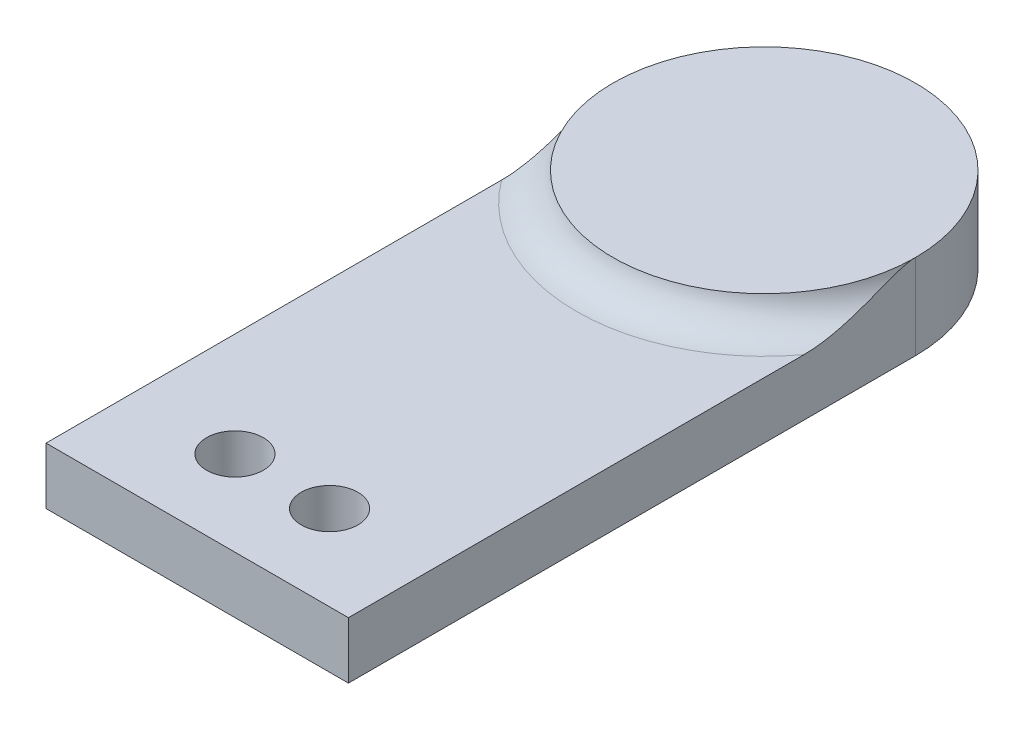
SolidWorks part; units mm, degrees
ref_plane "Plano frontal" through (0, 0, 0) normal (0, 0, 1) x (1, 0, 0)
ref_plane "Plano superior" through (0, 0, 0) normal (0, 1, 0) x (1, 0, 0)
ref_plane "Plano direito" through (0, 0, 0) normal (1, 0, 0) x (0, 0, -1)
sketch "Sketch1" plane through (0, 0, 0) normal (0, 1, 0) x (1, 0, 0)
  circle A0 centre (0, 0) radius 8
  dimension "D1" = 16
extrude "Boss-Extrude1" add sketch "Sketch1" against normal blind 1.5 and the other way blind 3
sketch "Sketch2" plane through (0, 0, 0) normal (0, 1, 0) x (1, 0, 0)
  line L1 (-8, 0) -> (8, 0)
  line L2 (-8, 0) -> (-8, -30)
  line L3 (-8, -30) -> (8, -30)
  line L4 (8, 0) -> (8, -30)
  circle A1 centre (0, 0) radius 8 construction
  dimension "D1" = 30
extrude "Boss-Extrude2" add sketch "Sketch2" along normal mid plane 3
sketch "Sketch3" plane through (0, -1.5, 0) normal (0, -1, 0) x (-1, 0, 0)
  line L1 (8, -30) -> (-8, -30) construction
  circle A0 centre (2.5031, -25.5) radius 1.5
  circle A1 centre (-2.5031, -25.5) radius 1.5
  dimension "D4" = 3
  dimension "D5" = 3
  dimension "D1" = 2.5031
  dimension "D2" = 2.5031
  dimension "D3" = 4.5
extrude "Cut-Extrude1" cut sketch "Sketch3" against normal up to next
sketch "Sketch4" plane through (0, -1.5, 0) normal (0, -1, 0) x (-1, 0, 0)
  line L0 (-3.3, 0) -> (3.3, 0)
  circle A0 centre (0, 0) radius 3.3
  dimension "D1" = 6.6
revolve "Cut-Revolve21" cut sketch "Sketch4" angle 360 about L0 region at (0, -1.5, 1.4006)
fillet "Fillet1" radius 2 1 edges at (0, 1.5, 8)
equation "\"D2@Sketch3\"=\"D1@Sketch3\""
equation "\"D5@Sketch3\"=\"D4@Sketch3\""
equation "\"D4@Sketch3\"=3"
